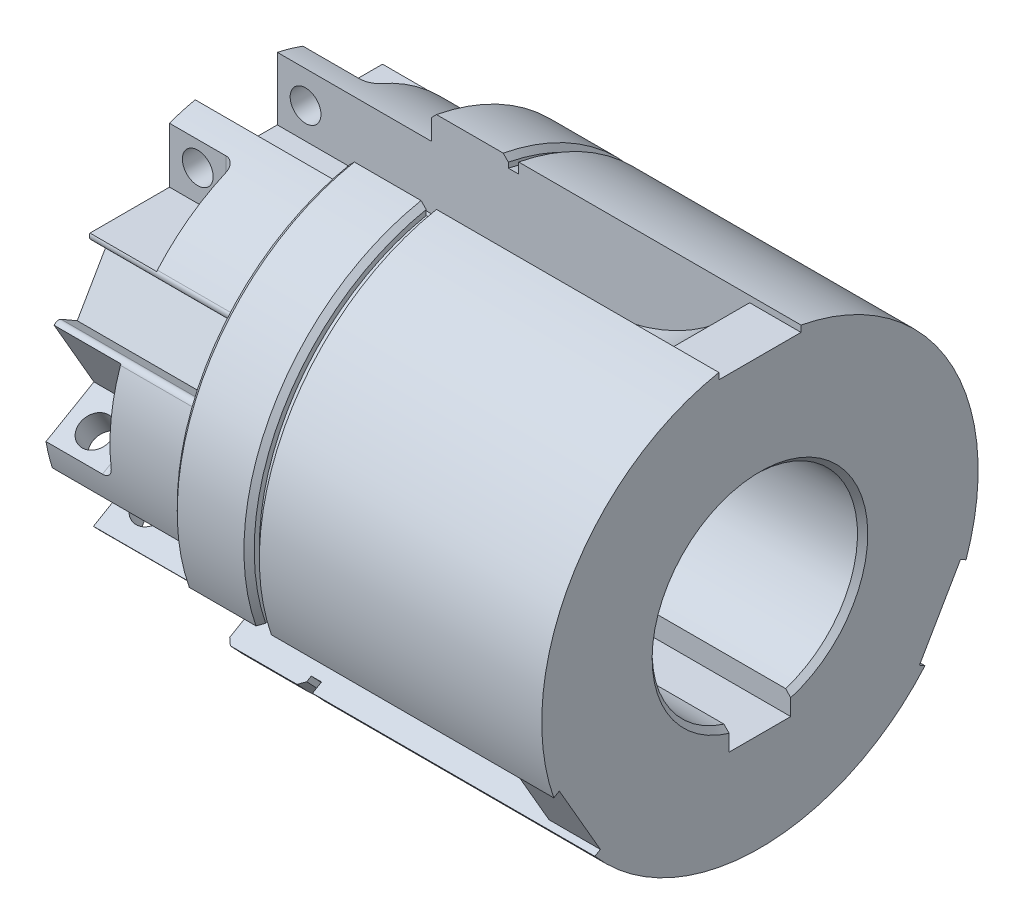
SolidWorks part; units mm, degrees
material "1.0060 (E335)"
ref_plane "Front Plane" through (0, 0, 0) normal (0, 0, 1) x (1, 0, 0)
ref_plane "Top Plane" through (0, 0, 0) normal (0, 1, 0) x (1, 0, 0)
ref_plane "Right Plane" through (0, 0, 0) normal (1, 0, 0) x (0, 0, -1)
sketch "Sketch1" plane through (0, 0, 0) normal (0, 0, 1) x (1, 0, 0)
  line L0 (-534.701, 0) -> (26200.3507, 0) construction
  line L1 (0, 20) -> (0, 42.5)
  line L2 (0, 20) -> (-102, 20)
  line L3 (0, 42.5) -> (-55, 42.5)
  line L4 (-55, 42.5) -> (-55, 40.5)
  line L5 (-55, 40.5) -> (-57, 40.5)
  line L6 (-57, 40.5) -> (-57, 42.5)
  line L7 (-57, 42.5) -> (-72, 42.5)
  line L8 (-72, 42.5) -> (-72, 37.6)
  line L9 (-72, 37.6) -> (-102, 37.6)
  line L10 (-102, 37.6) -> (-102, 20)
  dimension "D1" = 40
  dimension "D2" = 75.2
  dimension "D3" = 2
  dimension "D4" = 2
  dimension "D5" = 15
  dimension "D7" = 85
  dimension "D8" = 30
  dimension "D9" = 55
revolve "Revolve1" add sketch "Sketch1" angle 360 about L0
sketch "Sketch3" plane through (0, 0, 0) normal (0, 0, 1) x (1, 0, 0)
  line L0 (-102, 24.5) -> (-42, 24.5)
  line L1 (-102, 37.6) -> (-102, -37.6) construction
  line L2 (0, 42.5) -> (-55, 42.5) construction
  line L3 (0, 42.5) -> (-55, 42.5)
  line L4 (-57, -42.5) -> (-57, 42.5) construction
  line L5 (-55, 42.5) -> (-55, -42.5) construction
  line L6 (-57, 40.5) -> (-57, 42.5)
  line L7 (-55, 42.5) -> (-55, 40.5)
  line L8 (-55, 40.5) -> (-57, 40.5) construction
  line L9 (-55, 40.5) -> (-57, 40.5)
  line L10 (-72, 37.6) -> (-102, 37.6) construction
  line L11 (-72, 42.5) -> (-72, -42.5) construction
  line L12 (-57, 42.5) -> (-72, 42.5) construction
  line L13 (-72, 37.6) -> (-102, 37.6)
  line L14 (-72, 42.5) -> (-72, 37.6)
  line L15 (-57, 42.5) -> (-72, 42.5)
  line L16 (-102, 37.6) -> (-102, 24.5)
  line L17 (-10, 40.5) -> (0, 40.5)
  line L18 (0, -42.5) -> (0, 42.5) construction
  line L19 (0, 40.5) -> (0, 42.5)
  arc A0 (-42, 24.5) -> (-10, 40.5) centre (-42, 64.5) ccw
  dimension "D2" = 40
  dimension "D1" = 18
  dimension "D3" = 2
  dimension "D4" = 60
extrude "Cut-Extrude1" cut sketch "Sketch3" against normal mid plane 16
pattern_circular "CirPattern1" count 3 over 360 about axis through (0, 0, 0) along (-1, 0, 0) of "Cut-Extrude1"
sketch "Sketch4" plane through (-102, 0, 0) normal (-1, 0, 0) x (0, 0, 1)
  line L0 (-13, 35.2812) -> (-13, 24.5)
  line L1 (-13, 24.5) -> (-28.5221, 24.5)
  line L2 (-8, 24.5) -> (8, 24.5) construction
  line L3 (0, -1000) -> (0, 49000) construction
  line L4 (-8, 24.5) -> (-8, 40.5) construction
  line L5 (13, 35.2812) -> (13, 24.5)
  line L6 (13, 24.5) -> (28.5221, 24.5)
  arc A0 (-8, 36.7391) -> (-35.817, -11.4413) centre (0, 0) ccw construction
  arc A1 (-8, 36.7391) -> (-35.817, -11.4413) centre (0, 0) ccw construction
  arc A2 (-13, 35.2812) -> (-28.5221, 24.5) centre (0, 0) ccw
  arc A3 (13, 35.2812) -> (28.5221, 24.5) centre (0, 0) cw
  dimension "D1" = 5
extrude "Cut-Extrude2" cut sketch "Sketch4" against normal blind 13
fillet "Fillet1" radius 2 2 edges at (-89, 29.8906, -13) (-89, 29.8906, 13)
sketch "Sketch6" plane through (0, 0, 13) normal (0, 0, 1) x (1, 0, 0)
  line L0 (-91, 24.5) -> (-102, 24.5) construction
  circle A0 centre (-96.5, 30.5) radius 3
  point P2 (-96.5, 24.5)
  dimension "D1" = 6
  dimension "D2" = 6
extrude "Cut-Extrude3" cut sketch "Sketch6" against normal up to surface (26 mm away) up to face at (-96.5, 29.8906, -13)
pattern_circular "CirPattern2" count 3 over 360 about axis through (-534.701, 0, 0) along (-1, 0, 0) of "Cut-Extrude2", "Fillet1", "Cut-Extrude3" reverse direction yes
sketch "Sketch7" plane through (-102, 0, 0) normal (-1, 0, 0) x (0, 0, 1)
  line L0 (0, -1000) -> (0, 49000) construction
  line L1 (-6, -37.1182) -> (-6, -32.3)
  line L2 (-6, -32.3) -> (6, -32.3)
  line L3 (6, -32.3) -> (6, -37.1182)
  arc A0 (-27.817, -25.2977) -> (27.817, -25.2977) centre (0, 0) ccw construction
  arc A1 (-6.9566, -36.9509) -> (6.9566, -36.9509) centre (0, 0) ccw construction
  arc A2 (-6, -37.1182) -> (6, -37.1182) centre (0, 0) ccw
  point P8 (0, -32.3)
  dimension "D1" = 12
  dimension "D2" = 32.3
extrude "Cut-Extrude4" cut sketch "Sketch7" against normal up to surface (30 mm away) up to face at (-72, -33.299, 0)
fillet "Fillet2" radius 1 2 edges at (-87, -37.1182, 6) (-87, -37.1182, -6)
pattern_circular "CirPattern3" count 3 over 360 about axis through (-534.701, 0, 0) along (-1, 0, 0) of "Cut-Extrude4", "Fillet2" reverse direction yes
ref_plane "Plane1" through (0, -23.3, 0) normal (0, 1, 0) x (1, 0, 0)
sketch "Sketch9" plane through (0, -23.3, 0) normal (0, 1, 0) x (1, 0, 0)
  line L0 (-102, 8) -> (-102, -8) construction
  line L1 (-102, -6) -> (0, -6)
  line L2 (-102, -6) -> (-102, 6)
  line L3 (-102, 6) -> (0, 6)
  line L4 (0, -6) -> (0, 6)
  line L5 (0, 8) -> (0, -8) construction
  point P8 (-102, 0)
  dimension "D1" = 12
extrude "Cut-Extrude5" cut sketch "Sketch9" along normal up to next
chamfer "Chamfer2" distance 1 angle 45 2 edges at (0, 20, 0) (-102, 20, 0)
chamfer "Chamfer3" distance 1 angle 45 6 edges at (-57, 21.25, -36.8061) (-72, 21.25, -36.8061) (-57, -42.5, 0) (-72, -42.5, 0) (-57, 21.25, 36.8061) (-72, 21.25, 36.8061)
